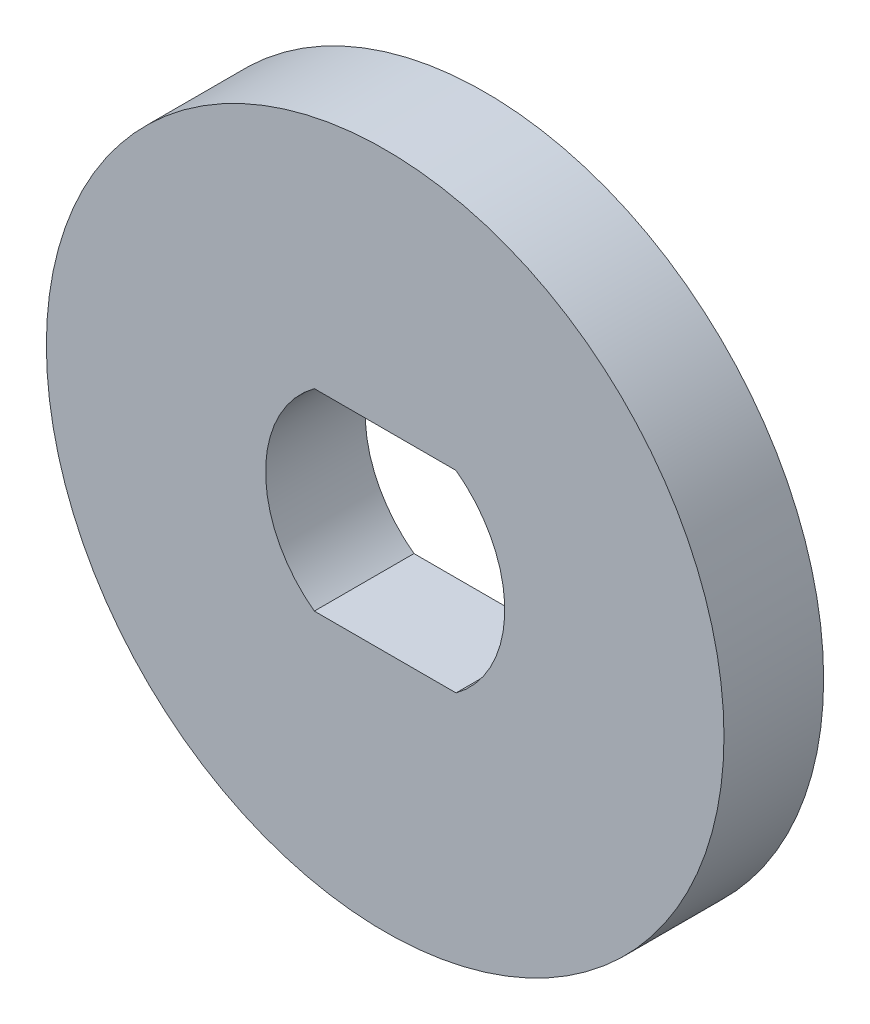
SolidWorks part; units mm, degrees
material "Polylactic Acid (PLA)"
ref_plane "Front Plane" through (0, 0, 0) normal (0, 0, 1) x (1, 0, 0)
ref_plane "Top Plane" through (0, 0, 0) normal (0, 1, 0) x (1, 0, 0)
ref_plane "Right Plane" through (0, 0, 0) normal (1, 0, 0) x (0, 0, -1)
sketch "Sketch1" plane through (0, 0, 0) normal (0, 0, 1) x (1, 0, 0)
  line L0 (-2.1331, 2.9) -> (2.1331, 2.9)
  line L1 (-1.9975, -2.5) -> (1.9975, -2.5) construction
  line L2 (-1.9975, -2.5) -> (-1.9975, 2.5) construction
  line L3 (-1.9975, 2.5) -> (1.9975, 2.5) construction
  line L4 (1.9975, -2.5) -> (1.9975, 2.5) construction
  line L5 (-1.9975, -2.5) -> (1.9975, 2.5) construction
  line L6 (-1.9975, 2.5) -> (1.9975, -2.5) construction
  line L7 (-2.1331, -2.9) -> (2.1331, -2.9)
  circle A0 centre (0, 0) radius 10.2
  arc A1 (-1.9975, 2.5) -> (-1.9975, -2.5) centre (0, 0) ccw construction
  arc A2 (1.9975, -2.5) -> (1.9975, 2.5) centre (0, 0) ccw construction
  arc A3 (2.1331, -2.9) -> (2.1331, 2.9) centre (0, 0) ccw
  arc A4 (-2.1331, 2.9) -> (-2.1331, -2.9) centre (0, 0) ccw
  dimension "D1" = 20.4
  dimension "D2" = 6.4
  dimension "D3" = 2.5
  dimension "D4" = 0.4
extrude "Boss-Extrude1" add sketch "Sketch1" along normal blind 3
